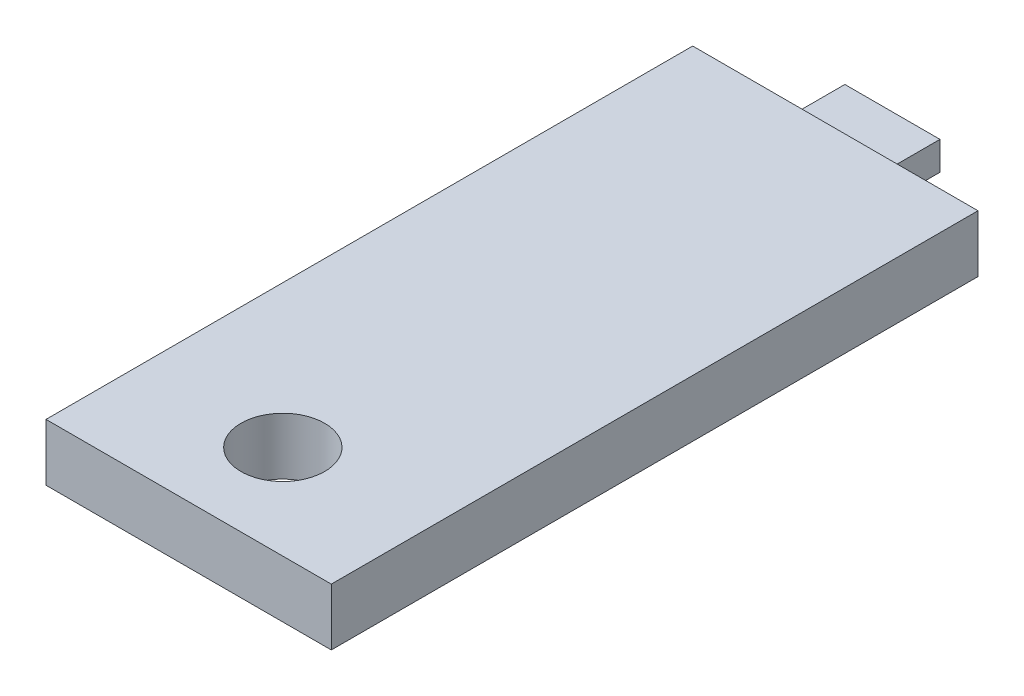
SolidWorks part; units mm, degrees
ref_plane "Front Plane" through (0, 0, 0) normal (0, 0, 1) x (1, 0, 0)
ref_plane "Top Plane" through (0, 0, 0) normal (0, 1, 0) x (1, 0, 0)
ref_plane "Right Plane" through (0, 0, 0) normal (1, 0, 0) x (0, 0, -1)
sketch "Sketch1" plane through (0, 0, 0) normal (0, 0, 1) x (1, 0, 0)
  line L1 (0, 0) -> (5, 0)
  line L2 (0, 0) -> (0, 1.5)
  line L3 (0, 1.5) -> (5, 1.5)
  line L4 (5, 0) -> (5, 1.5)
  dimension "D1" = 5
  dimension "D2" = 1.5
extrude "Boss-Extrude1" add sketch "Sketch1" along normal blind 3
sketch "Sketch2" plane through (0, 0, 3) normal (0, 0, 1) x (1, 0, 0)
  line L0 (0, 0) -> (5, 0) construction
  line L1 (-5, -0.75) -> (10, -0.75)
  line L2 (-5, -0.75) -> (-5, 2.25)
  line L3 (-5, 2.25) -> (10, 2.25)
  line L4 (10, -0.75) -> (10, 2.25)
  line L6 (5, 1.5) -> (0, 1.5) construction
  point P8 (2.5, 1.5)
  dimension "D1" = 15
  dimension "D2" = 3
  dimension "D3" = 0.75
  dimension "D4" = 7.5
extrude "Boss-Extrude2" add sketch "Sketch2" along normal blind 34
sketch "Sketch3" plane through (0, -0.75, 0) normal (0, -1, 0) x (1, 0, 0)
  line L0 (10, 37) -> (10, 3) construction
  circle A0 centre (2.5, 32.0499) radius 2.2
  dimension "D1" = 4.4
  dimension "D2" = 7.5
extrude "Cut-Extrude1" cut sketch "Sketch3" against normal through all
